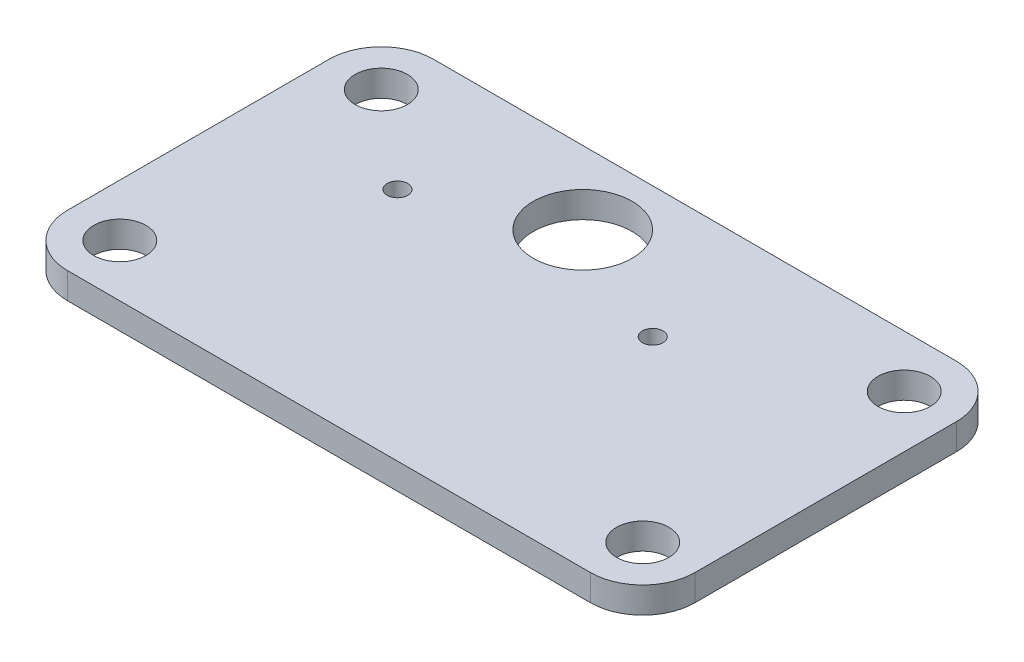
SolidWorks part; units mm, degrees
note: '?' marks a value the reader was unsure of.
ref_plane "Front Plane" through (0, 0, 0) normal (0, 0, 1) x (1, 0, 0)
ref_plane "Top Plane" through (0, 0, 0) normal (0, 1, 0) x (1, 0, 0)
ref_plane "Right Plane" through (0, 0, 0) normal (1, 0, 0) x (0, 0, -1)
sketch "Sketch1" plane through (0, 0, 0) normal (0, 1, 0) x (1, 0, 0)
  line L1 (36.5125, -28.575) -> (-26.9875, -28.575)
  line L2 (42.8625, -22.225) -> (42.8625, 9.525)
  line L3 (36.5125, 15.875) -> (-26.9875, 15.875)
  line L4 (-33.3375, -22.225) -> (-33.3375, 9.525)
  line L5 (42.8625, -28.575) -> (-33.3375, 15.875) construction
  line L6 (42.8625, 15.875) -> (-33.3375, -28.575) construction
  arc A0 (42.8625, 9.525) -> (36.5125, 15.875) centre (36.5125, 9.525) ccw
  arc A1 (36.5125, -28.575) -> (42.8625, -22.225) centre (36.5125, -22.225) ccw
  arc A2 (-26.9875, -28.575) -> (-33.3375, -22.225) centre (-26.9875, -22.225) cw
  arc A3 (-26.9875, 15.875) -> (-33.3375, 9.525) centre (-26.9875, 9.525) ccw
  point P0 (4.7625, -6.35)
  dimension "D3" = 6.35
  dimension "D1" = 76.2
  dimension "D2" = 44.45
  dimension "D4" = 6.35
  dimension "D5" = 4.7625
base flange "Base-Flange1" sketch "Sketch1" thickness 3.175 reverse thickness direction no parameters "D1"=0.7366
sketch "Sketch6" plane through (0, 0, 0) normal (0, 1, 0) x (1, 0, 0)
  circle A0 centre (-26.9875, 9.525) radius 3.175
  circle A1 centre (-26.9875, -22.225) radius 3.175
  circle A2 centre (36.5125, 9.525) radius 3.175
  circle A3 centre (36.5125, -22.225) radius 3.175
  circle A4 centre (0, 7) radius 6 construction
  circle A5 centre (0, 7) radius 6
  circle A6 centre (-15.5, 0) radius 1.25 construction
  circle A7 centre (15.5, 0) radius 1.25 construction
  circle A8 centre (-15.5, 0) radius 1.25
  circle A9 centre (15.5, 0) radius 1.25
  dimension "D1" = 6.35
extrude "Cut-Extrude1" cut sketch "Sketch6" against normal through all normal cut yes
ref_axis "Axis1" through (0, 0.1588, 0) along (0, -1, 0)?
sketch "Bend-Lines1" [suppressed] plane through (0, 0, 0) normal (0, 1, 0) x (1, 0, 0)
sketch "Bounding-Box1" [suppressed] plane through (0, 0, 0) normal (0, 1, 0) x (1, 0, 0)
sheet metal parameters "Sheet-Metal1" thickness 3.175 parameters "D1"=0.7366
flat pattern "Flat-Pattern1" [suppressed]
sketch "Bend-Lines2" plane through (0, 0, 0) normal (0, 1, 0) x (1, 0, 0)
sketch3d "Bounding-Box2" [suppressed]
  line L0 (146.05, -95.25, 0) -> (-6.35, -95.25, 0) construction
  line L1 (146.05, 6.35, 0) -> (-6.35, 6.35, 0) construction
  line L2 (146.05, -95.25, 0) -> (146.05, 6.35, 0) construction
  line L3 (-6.35, -95.25, 0) -> (-6.35, 6.35, 0) construction
sheet metal parameters "Sheet-Metal2" thickness 3.175 parameters "D1"=0.7366
flat pattern "Flat-Pattern1"
sketch "Bend-Lines2" plane through (0, 0, 0) normal (0, 1, 0) x (1, 0, 0)
sketch3d "Bounding-Box2" [suppressed]
  line L0 (-69.85, -38.1, 0) -> (6.35, -38.1, 0) construction
  line L1 (-69.85, 6.35, 0) -> (6.35, 6.35, 0) construction
  line L2 (-69.85, -38.1, 0) -> (-69.85, 6.35, 0) construction
  line L3 (6.35, -38.1, 0) -> (6.35, 6.35, 0) construction
